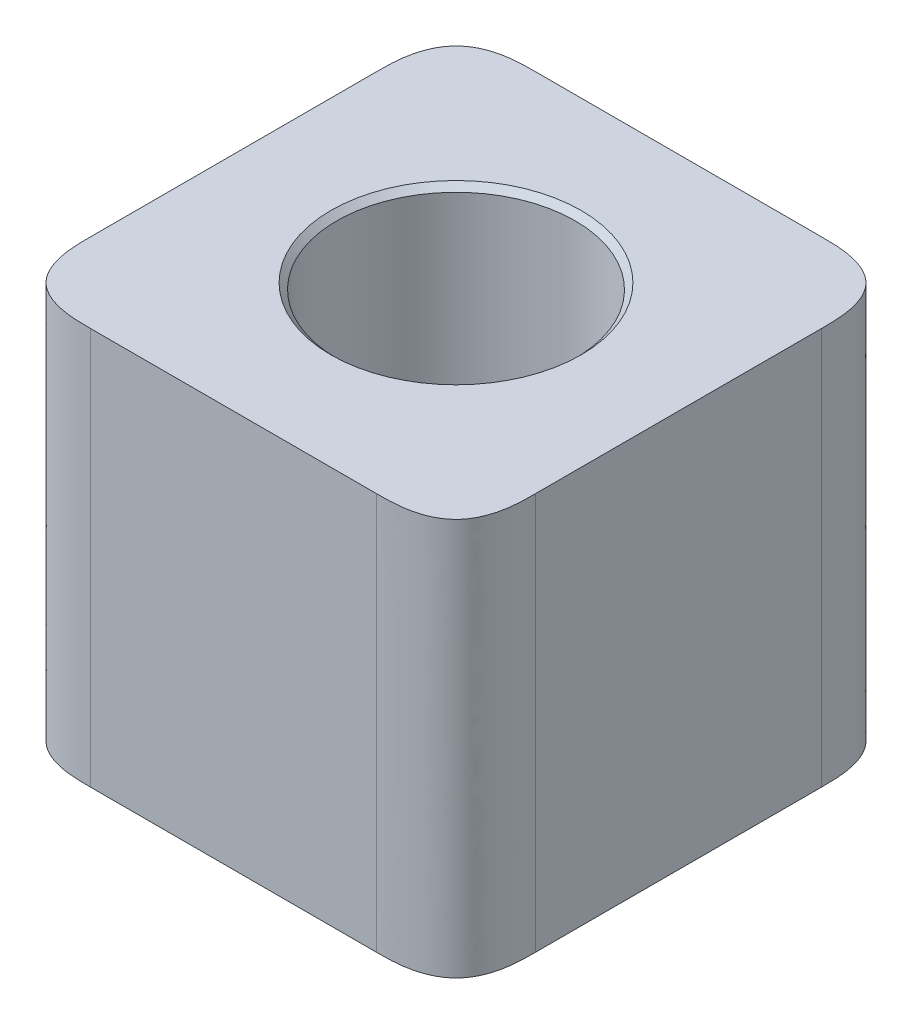
SolidWorks part; units mm, degrees
ref_plane "Front Plane" through (0, 0, 0) normal (0, 0, 1) x (1, 0, 0)
ref_plane "Top Plane" through (0, 0, 0) normal (0, 1, 0) x (1, 0, 0)
ref_plane "Right Plane" through (0, 0, 0) normal (1, 0, 0) x (0, 0, -1)
sketch "Sketch2" plane through (0, 0, 0) normal (0, 1, 0) x (1, 0, 0)
  line L0 (-5.3774, 3) -> (4.3662, 3) construction
  line L1 (-5.6, -5.6) -> (5.6, -5.6)
  line L2 (-5.6, -5.6) -> (-5.6, 5.6)
  line L3 (-5.6, 5.6) -> (5.6, 5.6)
  line L4 (5.6, -5.6) -> (5.6, 5.6)
  line L5 (-5.6, -5.6) -> (5.6, 5.6) construction
  line L6 (-5.6, 5.6) -> (5.6, -5.6) construction
  circle A0 centre (0, 0) radius 3
  dimension "D1" = 6
  dimension "D2" = 2.6
extrude "Boss-Extrude1" add sketch "Sketch2" along normal blind 9
sketch "Sketch3" plane through (0, 0, 0) normal (0, -1, 0) x (1, 0, 0)
  line L1 (-5.6, 5.6) -> (5.6, 5.6)
  line L2 (-5.6, 5.6) -> (-5.6, -5.6)
  line L3 (-5.6, -5.6) -> (5.6, -5.6)
  line L4 (5.6, 5.6) -> (5.6, -5.6)
extrude "Boss-Extrude2" add sketch "Sketch3" along normal blind 1
fillet "Fillet1" radius 2 4 edges at (5.6, 4, 5.6) (-5.6, 4, 5.6) (-5.6, 4, -5.6) (5.6, 4, -5.6)
hole_wizard "CSK for M3 Flat Head Machine Screw1" positions "Sketch5" profile "Sketch6" countersink size "M3" standard "ANSI Metric"
sketch "Sketch5" plane through (0, 9, 0) normal (0, 1, 0) x (1, 0, 0)
  point P0 (0, 0)
sketch "Sketch6" plane through (0, 9, 0) normal (1, 0, 0) x (0, 0, 1)
  line L0 (0, 0) -> (0, 10.0215)
  line L1 (0, 10.0215) -> (1.7, 9)
  line L2 (1.7, 9) -> (1.7, 1.45)
  line L3 (1.7, 1.45) -> (3.15, 0)
  line L5 (3.15, 0) -> (0, 0)
  line L6 (-1.7, 1.45) -> (-3.15, 0) construction
  line L10 (0, 10.0215) -> (-1.7, 9) construction
  line L11 (0, -6.35) -> (0, 107.95) construction
  dimension "Hole Dia." = 3.4
  dimension "Hole Depth" = 9
  dimension "Near C'Sink Dia." = 6.3
  dimension "Near C'Sink Angle" = 90
  dimension "Drill Angle" = 118
